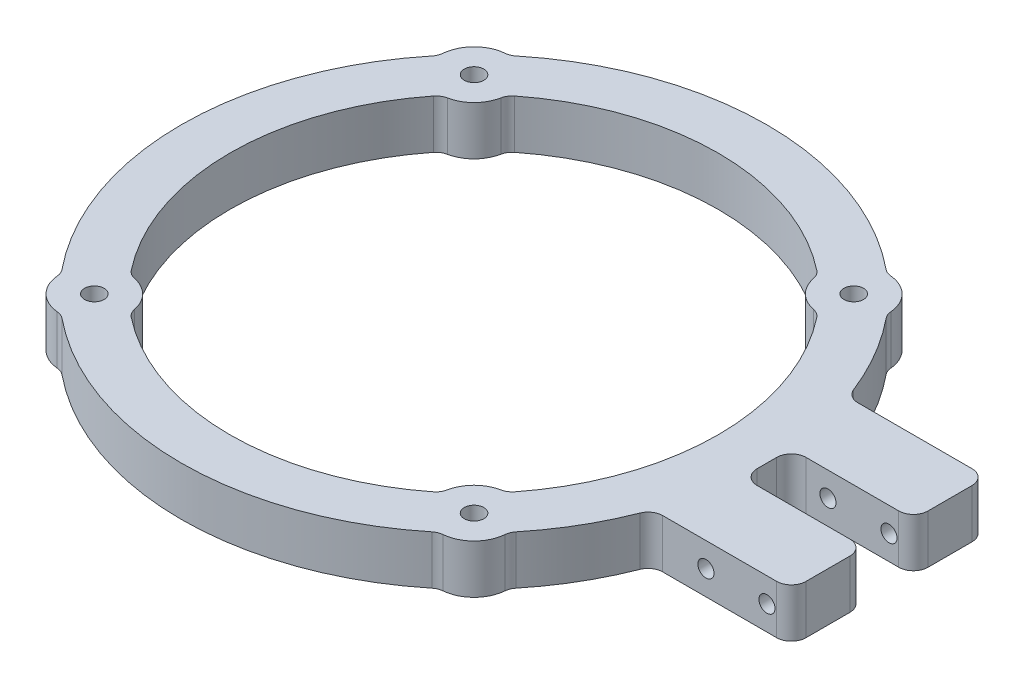
SolidWorks part; units mm, degrees
material "6063-T83"
ref_plane "Front Plane" through (0, 0, 0) normal (0, 0, 1) x (1, 0, 0)
ref_plane "Top Plane" through (0, 0, 0) normal (0, 1, 0) x (1, 0, 0)
ref_plane "Right Plane" through (0, 0, 0) normal (1, 0, 0) x (0, 0, -1)
sketch "Sketch1" plane through (0, 0, 0) normal (0, 1, 0) x (1, 0, 0)
  line L0 (0, -50) -> (0, -60) construction
  line L1 (0, 0) -> (0, -50) construction
  line L2 (56.5685, -20) -> (85, -20)
  line L3 (85, -20) -> (85, -5)
  line L4 (85, -5) -> (60, -5)
  line L5 (60, -5) -> (60, 5)
  line L6 (60, 5) -> (85, 5)
  line L7 (85, 5) -> (85, 20)
  line L8 (85, 20) -> (56.5685, 20)
  circle A0 centre (0, 0) radius 50
  circle A1 centre (0, 0) radius 60 construction
  arc A2 (56.5685, 20) -> (56.5685, -20) centre (0, 0) ccw
  dimension "D1" = 100
  dimension "D2" = 10
  dimension "D3" = 10
  dimension "D4" = 15
  dimension "D6" = 25
extrude "Boss-Extrude1" add sketch "Sketch1" along normal blind 10
sketch "Sketch3" plane through (0, 10, 0) normal (0, 1, 0) x (1, 0, 0)
  line L0 (38.8909, 38.8909) -> (38.8909, -38.8909) construction
  line L1 (60, -5) -> (60, 5) construction
  circle A0 centre (0, 0) radius 55 construction
  circle A1 centre (38.8909, -38.8909) radius 7
  circle A2 centre (-38.8909, -38.8909) radius 7
  circle A3 centre (-38.8909, 38.8909) radius 7
  circle A4 centre (38.8909, 38.8909) radius 7
  point P14 (0, 0)
  dimension "D1" = 110
  dimension "D2" = 14
  dimension "D3" = 4
extrude "Boss-Extrude2" add sketch "Sketch3" against normal up to surface (10 mm away) up to face at (57.0711, 0, 0)
sketch "Sketch4" plane through (0, 10, 0) normal (0, 1, 0) x (1, 0, 0)
  circle A0 centre (38.8909, -38.8909) radius 2
  circle A1 centre (-38.8909, -38.8909) radius 2
  circle A2 centre (-38.8909, 38.8909) radius 2
  circle A3 centre (38.8909, 38.8909) radius 2
  point P12 (0, 0)
  dimension "D1" = 4
  dimension "D2" = 4
extrude "Cut-Extrude1" cut sketch "Sketch4" against normal blind 10
hole_wizard "M4x0.7 Tapped Hole1" positions "Sketch7" profile "Sketch8" tap size "M4x0.7" standard "ANSI Metric" end condition through all
sketch "Sketch7" plane through (0, 0, 5) normal (0, 0, -1) x (-1, 0, 0)
  line L0 (-85, 5) -> (-60, 5) construction
  line L1 (-85, 10) -> (-85, 0) construction
  line L2 (-60, 10) -> (-60, 0) construction
  point P0 (-80, 5)
  point P2 (-67.5, 5)
  dimension "D1" = 5
  dimension "D2" = 7.5
sketch "Sketch8" plane through (80, 5, 5) normal (1, 0, 0) x (0, 1, 0)
  line L0 (0, 0) -> (0, 55)
  line L1 (0, 55) -> (1.65, 55)
  line L2 (1.65, 55) -> (1.65, 0)
  line L5 (1.65, 0) -> (0, 0)
  line L11 (0, -6.35) -> (0, 107.95) construction
  dimension "Thru Tap Drill Dia." = 3.3
  dimension "Thru Tap Drill Depth" = 55
cosmetic thread "Hole Thread1" parameters "D2"=4
cosmetic thread "Hole Thread2" parameters "D2"=4
hole_wizard "M4x0.7 Tapped Hole2" positions "Sketch9" profile "Sketch10" tap size "M4x0.7" standard "ANSI Metric" end condition through all
sketch "Sketch9" plane through (0, 0, -5) normal (0, 0, 1) x (1, 0, 0)
  line L0 (85, 5) -> (60, 5) construction
  line L1 (85, 10) -> (85, 0) construction
  line L2 (60, 10) -> (60, 0) construction
  point P0 (80, 5)
  point P2 (67.5, 5)
  dimension "D1" = 7.5
  dimension "D2" = 5
sketch "Sketch10" plane through (80, 5, -5) normal (1, 0, 0) x (0, -1, 0)
  line L0 (0, 0) -> (0, 55)
  line L1 (0, 55) -> (1.65, 55)
  line L2 (1.65, 55) -> (1.65, 0)
  line L5 (1.65, 0) -> (0, 0)
  line L11 (0, -6.35) -> (0, 107.95) construction
  dimension "Thru Tap Drill Dia." = 3.3
  dimension "Thru Tap Drill Depth" = 55
cosmetic thread "Hole Thread3" parameters "D2"=4
cosmetic thread "Hole Thread4" parameters "D2"=4
fillet "Fillet1" radius 3 24 edges at (85, 5, -20) (85, 5, -5) (85, 5, 5) (85, 5, 20) (38.5003, 5, 31.9018) (31.9018, 5, 38.5003) (38.5003, 5, -31.9018) (31.9018, 5, -38.5003) (-38.5003, 5, -31.9018) (-31.9018, 5, -38.5003) (-45.887, 5, -38.6573) (-38.6573, 5, -45.887) (38.6573, 5, -45.887) (45.887, 5, -38.6573) (-31.9018, 5, 38.5003) (-38.5003, 5, 31.9018) (-45.887, 5, 38.6573) (-38.6573, 5, 45.887) (38.6573, 5, 45.887) (45.887, 5, 38.6573) (56.5685, 5, 20) (56.5685, 5, -20) (60, 5, 5) (60, 5, -5)
